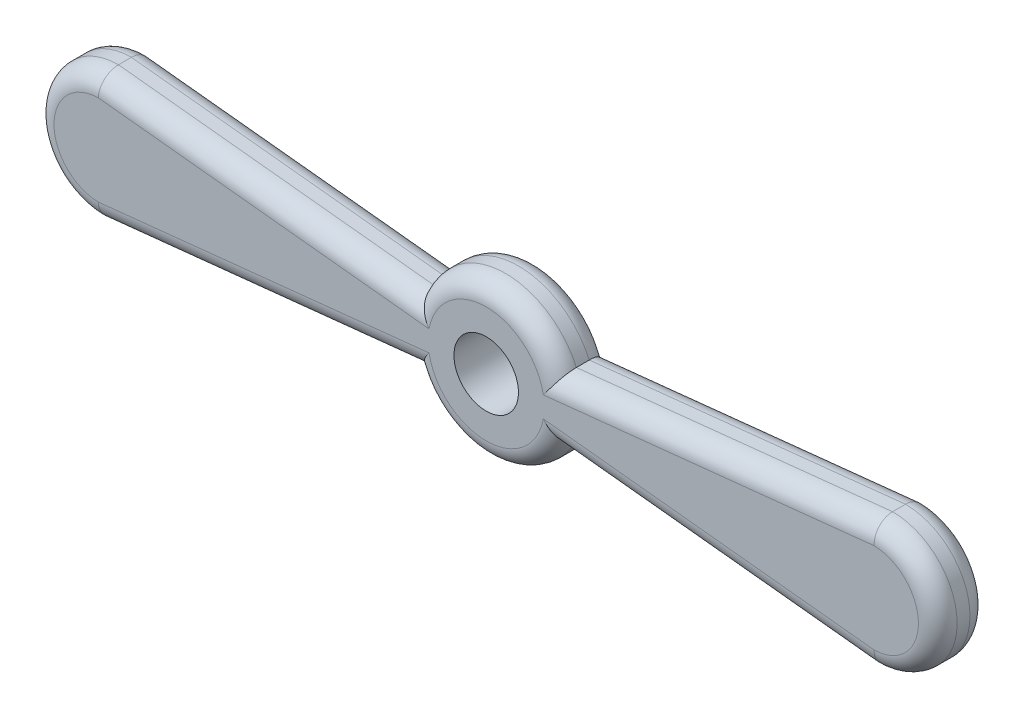
SolidWorks part; units mm, degrees
material "Mahogany"
ref_plane "Front" through (0, 0, 0) normal (0, 0, 1) x (1, 0, 0)
ref_plane "Top" through (0, 0, 0) normal (0, 1, 0) x (1, 0, 0)
ref_plane "Right" through (0, 0, 0) normal (1, 0, 0) x (0, 0, -1)
sketch "Sketch1" plane through (0, 0, 0) normal (0, 0, 1) x (1, 0, 0)
  line L0 (60, -10) -> (10.9773, -4.8475)
  line L1 (60, 10) -> (10.9773, 4.8475)
  line L2 (-10.9773, 4.8475) -> (-60, 10)
  line L3 (-10.9773, -4.8475) -> (-60, -10)
  arc A1 (60, 10) -> (60, -10) centre (60, 0) cw
  circle A2 centre (0, 0) radius 5
  arc A3 (-10.9773, -4.8475) -> (10.9773, -4.8475) centre (0, 0) ccw
  arc A4 (-60, 10) -> (-60, -10) centre (-60, 0) ccw
  arc A5 (10.9773, 4.8475) -> (-10.9773, 4.8475) centre (0, 0) ccw
  point P12 (-70, 0)
  dimension "D1" = 10
  dimension "D3" = 10
  dimension "D4" = 24
  dimension "D5" = 60
  dimension "D6" = 120
  dimension "D2" = 12
extrude "Boss-Extrude1" add sketch "Sketch1" along normal mid plane 8
fillet "Fillet1" radius 3 16 edges at (35.4887, 7.4238, 4) (70, 0, 4) (35.4887, -7.4238, 4) (0, -12, 4) (-35.4887, -7.4238, 4) (-70, 0, 4) (-35.4887, 7.4238, 4) (0, 12, 4) (35.4887, 7.4238, -4) (35.4887, -7.4238, -4) (-35.4887, -7.4238, -4) (0, -12, -4) (-35.4887, 7.4238, -4) (0, 12, -4) (-70, 0, -4) (70, 0, -4)
